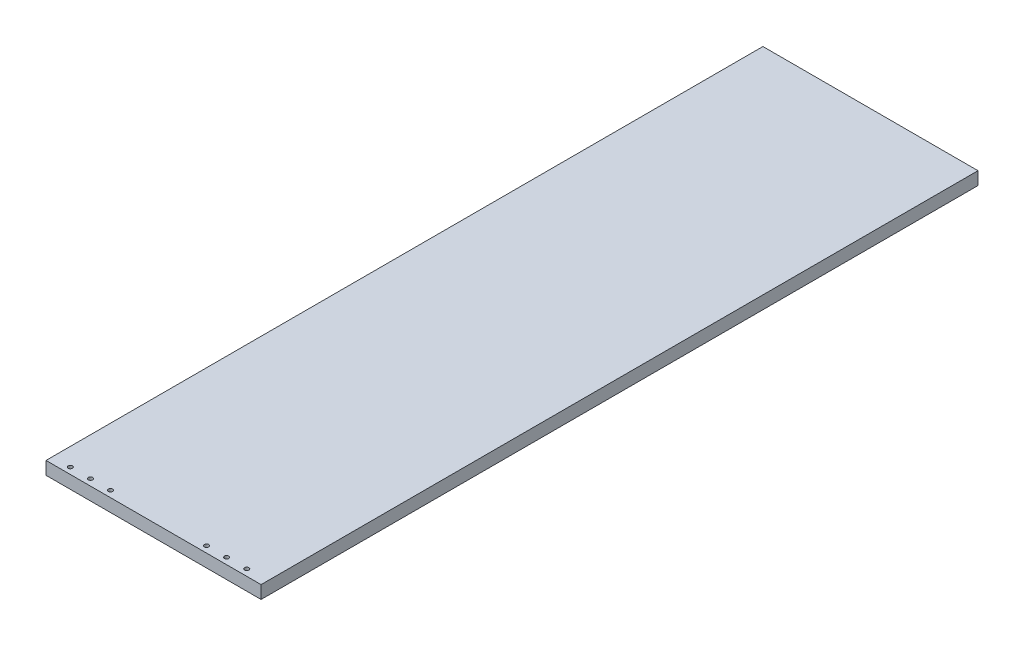
SolidWorks part; units mm, degrees
ref_plane "Спереди" through (0, 0, 0) normal (0, 0, 1) x (1, 0, 0)
ref_plane "Сверху" through (0, 0, 0) normal (0, 1, 0) x (1, 0, 0)
ref_plane "Справа" through (0, 0, 0) normal (1, 0, 0) x (0, 0, -1)
sketch "Эскиз2" plane through (0, 0, 0) normal (0, 1, 0) x (1, 0, 0)
  line L1 (0, 0) -> (300, 0)
  line L2 (0, 0) -> (0, 1000)
  line L3 (0, 1000) -> (300, 1000)
  line L4 (300, 0) -> (300, 1000)
extrude "Бобышка-Вытянуть1" add sketch "Эскиз2" along normal blind 18
sketch "Эскиз3" plane through (0, 18, 0) normal (0, 1, 0) x (1, 0, 0)
  circle A0 centre (25, 9) radius 3
  circle A1 centre (53, 9) radius 3
  circle A2 centre (81, 9) radius 3
  circle A3 centre (215, 9) radius 3
  circle A4 centre (243, 9) radius 3
  circle A5 centre (271, 9) radius 3
  dimension "D1" = 3
  dimension "D2" = 2
extrude "Вырез-Вытянуть1" cut sketch "Эскиз3" against normal blind 9
